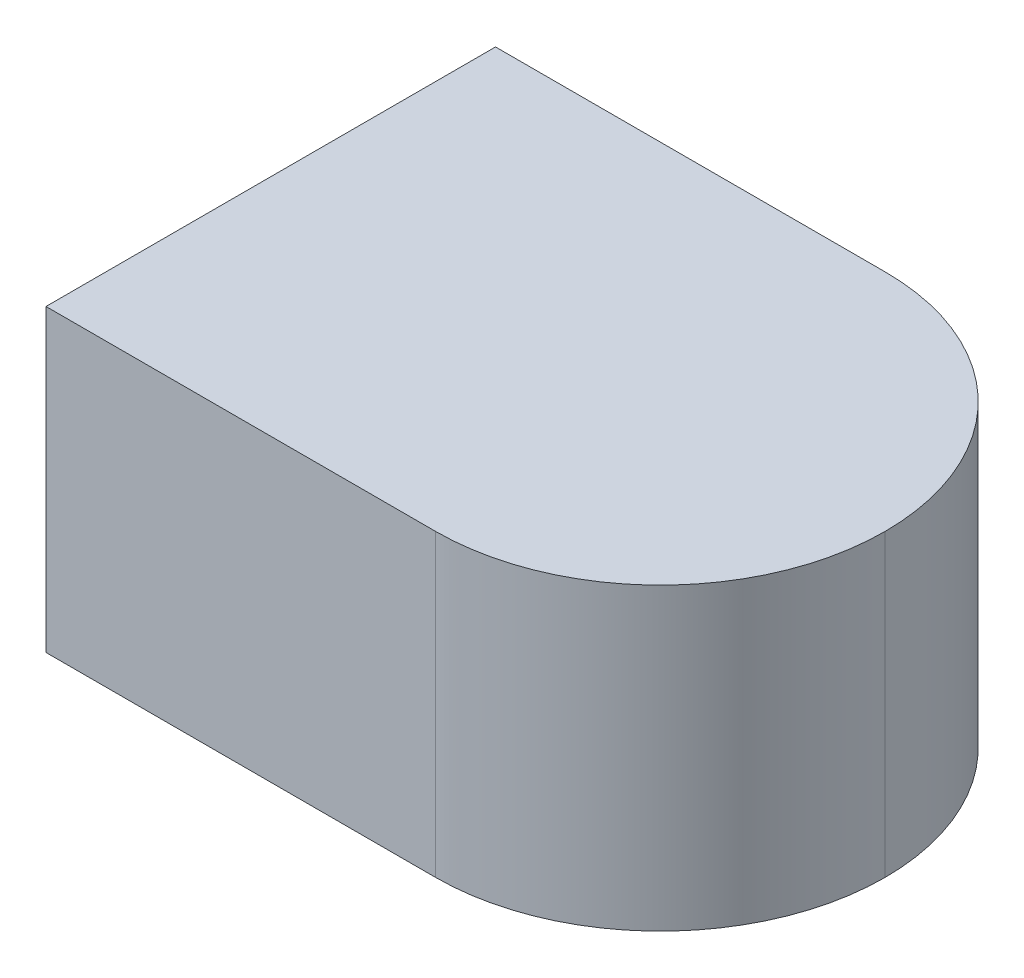
SolidWorks part; units mm, degrees
ref_plane "Front Plane" through (0, 0, 0) normal (0, 0, 1) x (1, 0, 0)
ref_plane "Top Plane" through (0, 0, 0) normal (0, 1, 0) x (1, 0, 0)
ref_plane "Right Plane" through (0, 0, 0) normal (1, 0, 0) x (0, 0, -1)
sketch "Sketch1" plane through (0, 0, 0) normal (0, 1, 0) x (1, 0, 0)
  line L1 (-0.205, -0.15) -> (0.205, -0.15)
  line L2 (-0.205, -0.15) -> (-0.205, 0.15)
  line L3 (-0.205, 0.15) -> (0.205, 0.15)
  line L4 (0.205, -0.15) -> (0.205, 0.15)
  line L5 (-0.205, -0.15) -> (0.205, 0.15) construction
  line L6 (-0.205, 0.15) -> (0.205, -0.15) construction
  point P0 (0, 0)
  point P8 (0, 0)
  point P9 (0, 0)
  point P10 (0, 0)
  point P11 (0.3878, 0)
  point P12 (0, 0)
  dimension "D1" = 0.3
  dimension "D2" = 0.41
extrude "Boss-Extrude1" add sketch "Sketch1" along normal blind 0.2
fillet "Fillet1" radius 0.15 2 edges at (0.205, 0.1, -0.15) (0.205, 0.1, 0.15)
